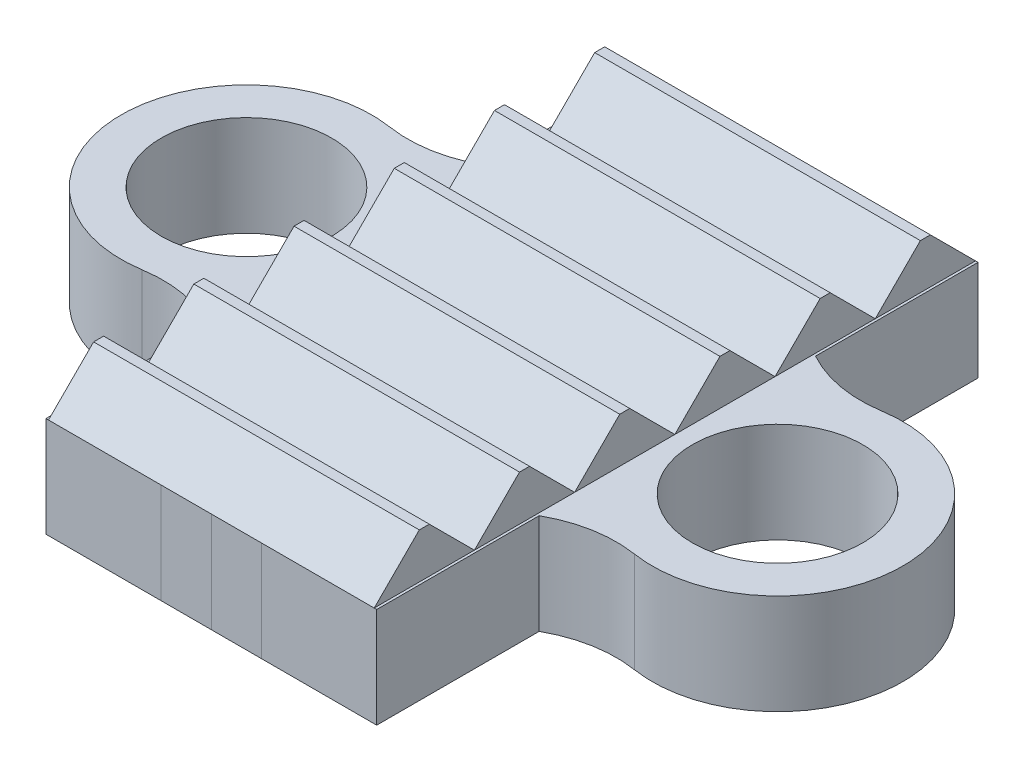
SolidWorks part; units mm, degrees
ref_plane "Alzado" through (0, 0, 0) normal (0, 0, 1) x (1, 0, 0)
ref_plane "Planta" through (0, 0, 0) normal (0, 1, 0) x (1, 0, 0)
ref_plane "Vista lateral" through (0, 0, 0) normal (1, 0, 0) x (0, 0, -1)
sketch "Croquis1" plane through (0, 0, 0) normal (0, 1, 0) x (1, 0, 0)
  line L0 (0, -16.4018) -> (0, 78.9163) construction
  line L1 (-63.9099, 0) -> (63.9099, 0) construction
  line L2 (-3.3, 6) -> (3.3, 6)
  line L3 (3.3, 6) -> (3.3, 2.7581)
  line L4 (-3.3, -6) -> (3.3, -6)
  line L5 (3.3, -6) -> (3.3, -2.7581)
  line L6 (-3.3, -6) -> (-3.3, -2.7581)
  line L7 (-3.3, 6) -> (-3.3, 2.7581)
  line L8 (3.3, -2.7581) -> (3.3, 2.7581)
  line L9 (-3.3, -2.7581) -> (-3.3, 2.7581)
  circle A0 centre (5.3, 0) radius 1.7
  arc A1 (4.911, -2.4695) -> (4.911, 2.4695) centre (5.3, 0) ccw
  arc A2 (3.3, 2.7581) -> (4.911, 2.4695) centre (4.5219, 4.9391) ccw
  arc A3 (3.3, -2.7581) -> (4.911, -2.4695) centre (4.5219, -4.9391) cw
  arc A4 (-3.3, -2.7581) -> (-4.911, -2.4695) centre (-4.5219, -4.9391) ccw
  arc A5 (-3.3, 2.7581) -> (-4.911, 2.4695) centre (-4.5219, 4.9391) cw
  arc A6 (-4.911, -2.4695) -> (-4.911, 2.4695) centre (-5.3, 0) cw
  circle A7 centre (-5.3, 0) radius 1.7
  point P6 (7.8, 0)
  point P10 (8, 0)
  point P19 (0, 0)
  point P28 (0, -6)
  point P29 (-8, 0)
  point P30 (0, 6)
  dimension "D1" = 7.8
  dimension "D5" = 5
  dimension "D6" = 5
  dimension "D4" = 6
extrude "Saliente-Extruir1" add sketch "Croquis1" along normal blind 2 contours L9 L6 L4 L5 L8 L3 L2 L7 | L8 A3 A1 A2 A0 | A6 A4 L9 A5 A7 region at (0, 0, 0) region at (-3.3712, 0, 0) region at (4.0687, 0, -2.4082)
ref_plane "Plano1" through (3.25, 0, 0) normal (1, 0, 0) x (0, 0, -1)
sketch "Croquis4" plane through (3.25, 0, 0) normal (1, 0, 0) x (0, 0, -1)
  line L0 (-6, 2) -> (-4, 2)
  line L1 (-6, 2) -> (-5.1, 2.9)
  line L2 (-5, 3) -> (-5, 2) construction
  line L3 (-4, 2) -> (-4.9, 2.9)
  line L4 (-5.1, 2.9) -> (-4.9, 2.9)
  dimension "D1" = 1
  dimension "D2" = 1
  dimension "D3" = 0.9
extrude "Saliente-Extruir2" add sketch "Croquis4" against normal blind 6.5
pattern_linear "MatrizL1" count 6 spacing 2 along (0, 0, -1) of "Saliente-Extruir2"
sketch "Sketch1" plane through (0, 0, 6) normal (0, 0, 1) x (1, 0, 0)
  line L0 (0, 2) -> (0, 0)
  line L1 (-3.25, 2) -> (3.25, 2) construction
  line L4 (-1, 2) -> (1, 2)
  line L5 (-1, 2) -> (-1, 0)
  line L6 (-1, 0) -> (1, 0)
  line L7 (1, 2) -> (1, 0)
  line M7 (3.25, 2) -> (-3.25, 2)
  dimension "D1" = 1
  dimension "D2" = 1
extrude "Cut-Extrude1" cut sketch "Sketch1" against normal blind 0.1 contours L7 L0 M7 | L5 L0 M7 region at (0.5, 1, 6) region at (-0.5, 1, 6)
extrude "Boss-Extrude1" add sketch "Sketch1<3>" against normal blind 0.1 separate body contours L7 L0 M7 region at (0.5, 1, 6)
sketch "Sketch1<3>" plane through (0, 0, 6) normal (0, 0, 1) x (1, 0, 0) same geometry as "Sketch1"
extrude "Boss-Extrude2" add sketch "Sketch1<4>" against normal blind 0.1 separate body contours L5 L0 M7 region at (-0.5, 1, 6)
sketch "Sketch1<4>" plane through (0, 0, 6) normal (0, 0, 1) x (1, 0, 0) same geometry as "Sketch1"
